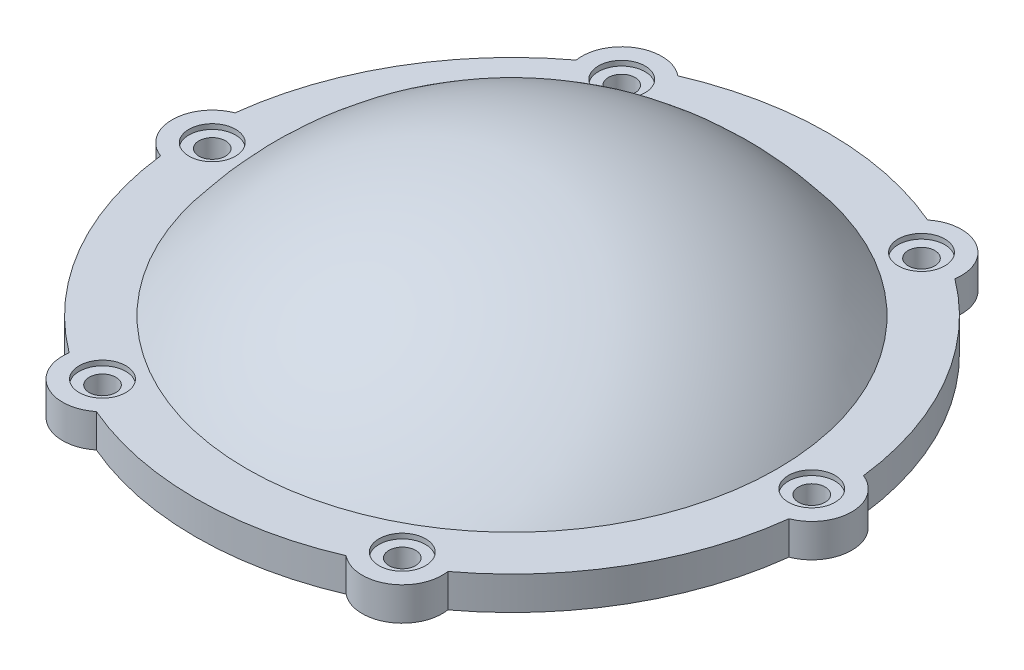
SolidWorks part; units mm, degrees
ref_plane "前基準面" through (0, 0, 0) normal (0, 0, 1) x (1, 0, 0)
ref_plane "上基準面" through (0, 0, 0) normal (0, 1, 0) x (1, 0, 0)
ref_plane "右基準面" through (0, 0, 0) normal (1, 0, 0) x (0, 0, -1)
sketch "草圖1" plane through (0, 0, 0) normal (0, 0, 1) x (1, 0, 0)
  line L0 (0, 0) -> (0, -23.75) construction
  line L1 (0, 0) -> (0, 26.25) construction
  line L2 (39.8113, 6.5) -> (47.5, 6.5)
  line L3 (47.5, 6.5) -> (47.5, 1.5)
  line L4 (40, 0.9279) -> (40, 0)
  line L5 (40, 0) -> (42, 0)
  line L6 (42, 0) -> (42, 1.5)
  line L7 (42, 1.5) -> (47.5, 1.5)
  line L8 (0, 26.25) -> (0, 23.25)
  line L9 (-47.5, 6.5) -> (-47.5, 1.5) construction
  line L10 (-42, 0) -> (-42, 1.5) construction
  line L11 (-40, 0.9279) -> (-40, 0) construction
  line L12 (0, 0) -> (53.8518, 0) construction
  arc A0 (0, 26.25) -> (39.8113, 6.5) centre (0, -23.75) cw
  arc A1 (0, 23.25) -> (40, 0.9279) centre (0, -23.75) cw
  arc A2 (0, 26.25) -> (24.7515, 19.6938) centre (0, -23.75) cw construction
  arc A3 (0, 23.25) -> (23.2664, 17.0872) centre (0, -23.75) cw construction
  point P10 (41, 0)
  dimension "D2" = 50
  dimension "D1" = 26.25
  dimension "D4" = 6.5
  dimension "D5" = 1.5
  dimension "D6" = 80
  dimension "D7" = 84
  dimension "D8" = 95
  dimension "D3" = 3
revolve "旋轉1" add sketch "草圖1" angle 360 about L1
sketch "草圖3" plane through (0, 6.5, 0) normal (0, 1, 0) x (1, 0, 0)
  line L0 (0, 0) -> (53.8518, 0) construction
  circle A2 centre (0, 0) radius 45 construction
  arc A4 (44.6, 5.9867) -> (44.6, -5.9867) centre (45, 0) cw
  arc A5 (44.6, 5.9867) -> (44.6, -5.9867) centre (0, 0) cw
  arc A6 (27.4846, -35.6314) -> (17.1154, -41.6181) centre (22.5, -38.9711) cw
  arc A7 (27.4846, -35.6314) -> (17.1154, -41.6181) centre (0, 0) cw
  arc A8 (-17.1154, -41.6181) -> (-27.4846, -35.6314) centre (-22.5, -38.9711) cw
  arc A9 (-17.1154, -41.6181) -> (-27.4846, -35.6314) centre (0, 0) cw
  arc A10 (-44.6, -5.9867) -> (-44.6, 5.9867) centre (-45, 0) cw
  arc A11 (-44.6, -5.9867) -> (-44.6, 5.9867) centre (0, 0) cw
  arc A12 (-27.4846, 35.6314) -> (-17.1154, 41.6181) centre (-22.5, 38.9711) cw
  arc A13 (-27.4846, 35.6314) -> (-17.1154, 41.6181) centre (0, 0) cw
  arc A14 (17.1154, 41.6181) -> (27.4846, 35.6314) centre (22.5, 38.9711) cw
  arc A15 (17.1154, 41.6181) -> (27.4846, 35.6314) centre (0, 0) cw
  dimension "D1" = 90
  dimension "D2" = 6
  dimension "D4" = 6
extrude "填料-伸長1" add sketch "草圖3" against normal up to surface (5 mm away) up to face at (0, 1.5, -47.5)
sketch "草圖5" plane through (0, 0, 0) normal (0, 0, 1) x (1, 0, 0)
  line L0 (45, 6.5) -> (45, 0.7005) construction
  line L1 (48.5, 6.5) -> (48.5, 5.75)
  line L2 (39.8113, 6.5) -> (47.5, 6.5) construction
  line L3 (48.5, 5.75) -> (47, 5.75)
  line L4 (47, 5.75) -> (47, 1.5)
  line L5 (42, 1.5) -> (47.5, 1.5) construction
  line L6 (47, 1.5) -> (45, 1.5)
  line L7 (45, 6.5) -> (48.5, 6.5)
  line L8 (45, 6.5) -> (45, 1.5)
  dimension "D1" = 3.5
  dimension "D2" = 2
  dimension "D3" = 0.75
revolve "除料-旋轉1" cut sketch "草圖5" angle 360 about L0
pattern_circular "環狀複製排列1" count 6 every 60 about axis through (0, 0, 0) along (0, 1, 0) of "除料-旋轉1"
